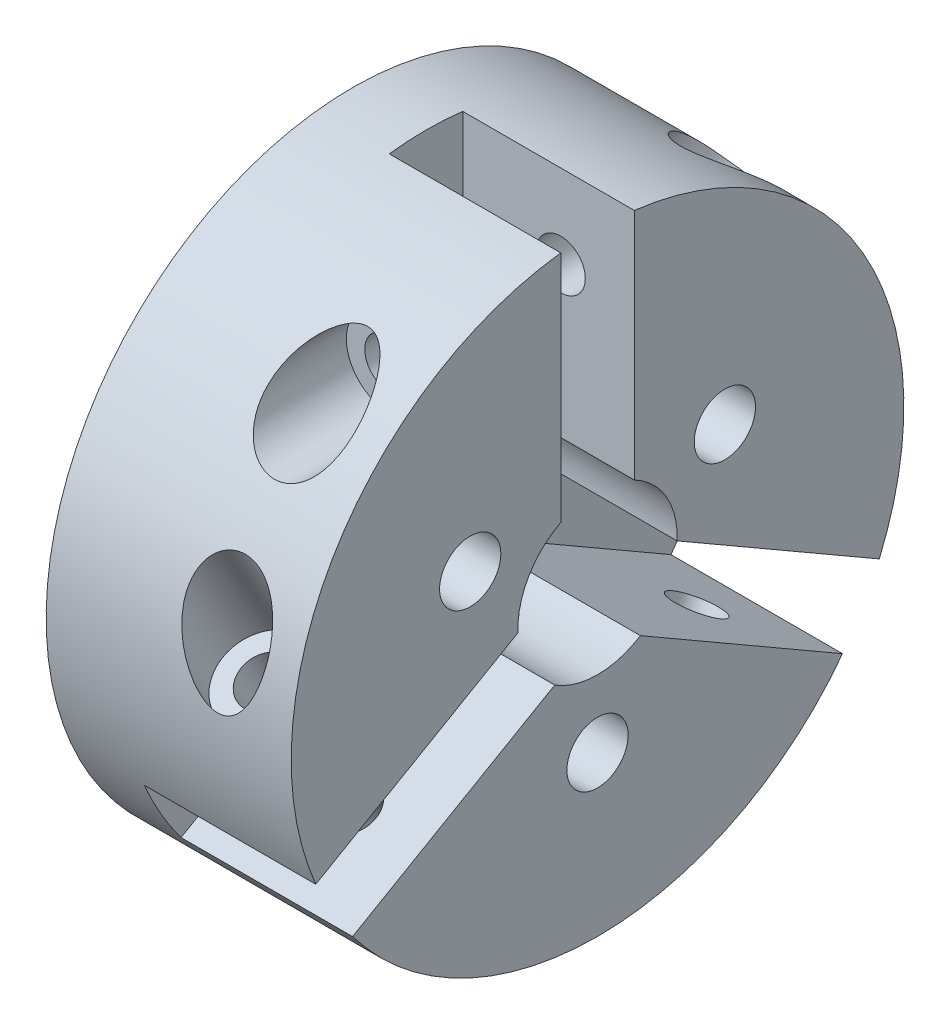
SolidWorks part; units mm, degrees
ref_plane "Front Plane" through (0, 0, 0) normal (0, 0, 1) x (1, 0, 0)
ref_plane "Top Plane" through (0, 0, 0) normal (0, 1, 0) x (1, 0, 0)
ref_plane "Right Plane" through (0, 0, 0) normal (1, 0, 0) x (0, 0, -1)
sketch "Sketch1" plane through (0, 0, 0) normal (1, 0, 0) x (0, 0, -1)
  line L0 (0, 0) -> (0, 125) construction
  line L1 (0, 125) -> (0, 0) construction
  line L2 (0, 0) -> (103.609, 0) construction
  line L3 (51.9615, 30) -> (0, 0) construction
  line L4 (17.4687, -27.4061) -> (100.7532, -75.4904)
  line L5 (-15, 28.8314) -> (-15, 125)
  line L6 (-15, 0) -> (-15, 125) construction
  line L7 (15, 28.8314) -> (15, 125)
  line L8 (32.4687, -1.4253) -> (115.7532, -49.5096)
  line L9 (0, 0) -> (108.2532, -62.5) construction
  line L10 (0, -60) -> (0, 0) construction
  line L11 (-32.4687, -1.4253) -> (-115.7532, -49.5096)
  line L12 (-17.4687, -27.4061) -> (-100.7532, -75.4904)
  line L13 (0, 0) -> (-108.2532, -62.5) construction
  line L14 (-51.9615, 30) -> (0, 0) construction
  circle A0 centre (0, 0) radius 125
  circle A1 centre (0, 0) radius 32.5
  circle A2 centre (51.9615, 30) radius 12.5
  circle A3 centre (0, -60) radius 12.5
  circle A4 centre (-51.9615, 30) radius 12.5
  point P30 (0, 0)
  dimension "D1" = 250
  dimension "D2" = 65
  dimension "D3" = 25
  dimension "D4" = 60
  dimension "D5" = 60
  dimension "D6" = 3
  dimension "D7" = 15
extrude "Boss-Extrude1" add sketch "Sketch1" along normal blind 30 contours A1 L5 A0 L11 A4 | A1 L11 A0 L12 | A1 L12 A0 L4 A3 | A1 L4 A0 L8 | A1 L8 A0 L7 A2 | A1 L7 A0 L5 | A1 region at (0, -38.9984, -67.5472) region at (0, -79.4749, 0) region at (0, 0, 0) region at (0, -38.9984, 67.5472) region at (0, 39.7375, -68.8273) region at (0, 39.7375, 68.8273) region at (0, 77.9968, 0)
extrude "Boss-Extrude2" add sketch "Sketch1<3>" along normal blind 100 contours A1 L5 A0 L11 A4 | A1 L8 A0 L7 A2 | A1 L12 A0 L4 A3 region at (0, -79.4749, 0) region at (0, 39.7375, -68.8273) region at (0, 39.7375, 68.8273)
sketch "Sketch1<3>" plane through (0, 0, 0) normal (1, 0, 0) x (0, 0, -1) same geometry as "Sketch1"
ref_plane "Plane1" through (0, 0, -150) normal (0, 0, 1) x (1, 0, 0)
sketch "Sketch5" plane through (0, 0, -150) normal (0, 0, 1) x (1, 0, 0)
  line L0 (0, 0) -> (100, 0) construction
  line L1 (100, 0) -> (70, 0) construction
  line L2 (70, 0) -> (70, 90) construction
  line L3 (100, -49.058) -> (100, 124.0967) construction
  circle A0 centre (70, 90) radius 17.5
  circle A1 centre (70, 90) radius 10
  point P6 (0, 0)
  point P7 (100, 0)
  dimension "D2" = 35
  dimension "D3" = 20
  dimension "D1" = 90
  dimension "D4" = 30
extrude "Cut-Extrude1" cut sketch "Sketch5" along normal offset from surface (95 mm away) 55 contours A1 | A0 A1 region at (52.995, 90, -150) region at (70, 90, -150) up to plane "Front Plane"
extrude "Cut-Extrude2" cut sketch "Sketch5<3>" along normal blind 150 contours A1 region at (70, 90, -150)
sketch "Sketch5<3>" plane through (0, 0, -150) normal (0, 0, 1) x (1, 0, 0) same geometry as "Sketch5"
pattern_circular "CirPattern1" count 3 over 360 about axis through (100, 0, 0) along (1, 0, 0) of "Cut-Extrude1", "Cut-Extrude2"
ref_plane "Plane3" through (0, 116.9134, -67.5) normal (0, 0.866, -0.5) x (1, 0, 0)
ref_plane "Plane4" through (0, 0, 0) normal (0, -0.866, 0.5) x (-1, 0, 0)
sketch "Sketch6" plane through (0, 116.9134, -67.5) normal (0, 0.866, -0.5) x (1, 0, 0)
  line L0 (0, 0) -> (100, 0) construction
  line L1 (100, 0) -> (70, 0) construction
  line L2 (70, 0) -> (70, 90) construction
  line L3 (0, 125) -> (0, -125) construction
  line L4 (100, -49.058) -> (100, 124.0967) construction
  circle A0 centre (70, 90) radius 17.5
  circle A1 centre (70, 90) radius 10
  point P6 (0, 0)
  point P7 (0, 20.7088)
  point P11 (78.7043, 90)
  point P12 (0, 0)
  dimension "D2" = 35
  dimension "D3" = 20
  dimension "D1" = 90
  dimension "D4" = 30
extrude "Cut-Extrude3" cut sketch "Sketch6" against normal offset from surface (80 mm away) 55 contours A1 | A0 A1 region at (52.995, 71.9134, -145.4423) region at (70, 71.9134, -145.4423) up to plane "Plane4"
extrude "Cut-Extrude4" cut sketch "Sketch6<3>" against normal blind 150 contours A1 region at (70, 71.9134, -145.4423)
sketch "Sketch6<3>" plane through (0, 116.9134, -67.5) normal (0, 0.866, -0.5) x (1, 0, 0) same geometry as "Sketch6"
pattern_circular "CirPattern2" count 3 over 360 about axis through (100, 0, 0) along (1, 0, 0) of "Cut-Extrude3", "Cut-Extrude4"
